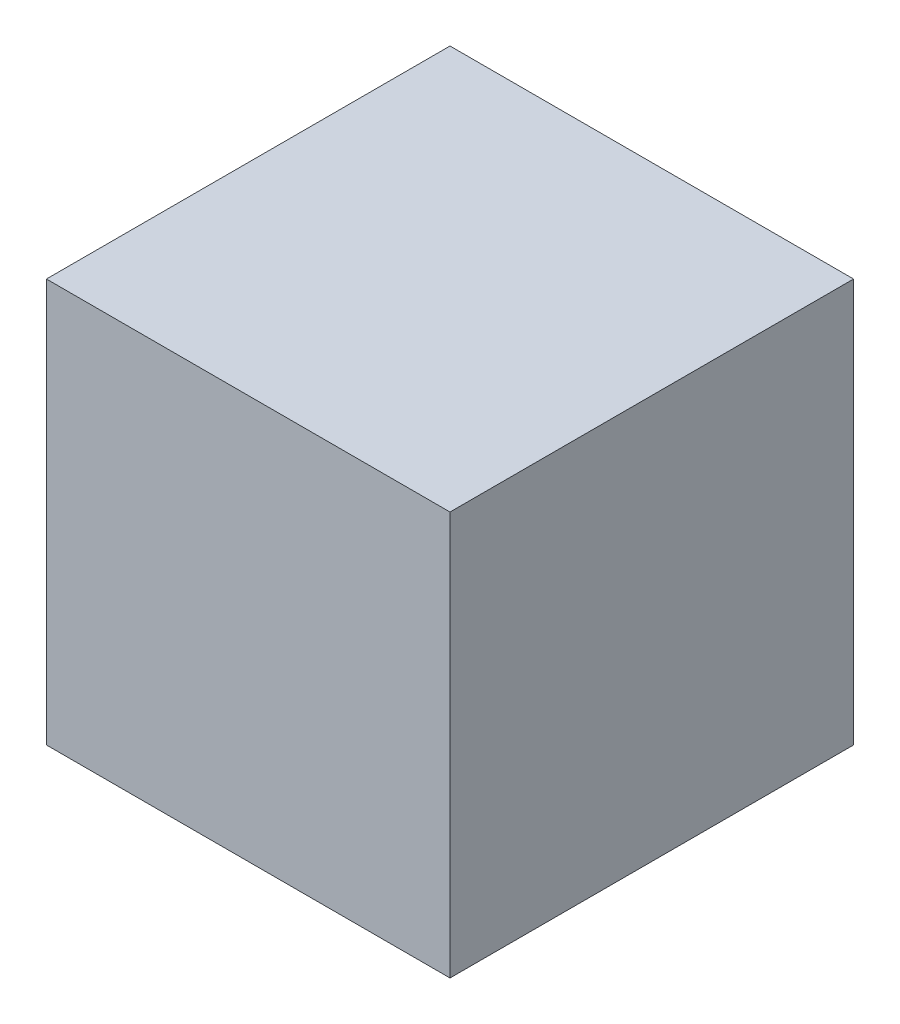
SolidWorks part; units mm, degrees
material "Plastiche personalizzate"
ref_plane "Piano frontale" through (0, 0, 0) normal (0, 0, 1) x (1, 0, 0)
ref_plane "Piano superiore" through (0, 0, 0) normal (0, 1, 0) x (1, 0, 0)
ref_plane "Piano destro" through (0, 0, 0) normal (1, 0, 0) x (0, 0, -1)
sketch "Schizzo1" plane through (0, 0, 0) normal (0, 0, 1) x (1, 0, 0)
  line L1 (50, -50) -> (-50, -50)
  line L2 (50, -50) -> (50, 50)
  line L3 (50, 50) -> (-50, 50)
  line L4 (-50, -50) -> (-50, 50)
  line L5 (50, -50) -> (-50, 50) construction
  line L6 (50, 50) -> (-50, -50) construction
  point P0 (0, 0)
  dimension "D1" = 100
  dimension "D2" = 100
extrude "Estrusione-Estrusione1" add sketch "Schizzo1" along normal blind 100
ref_plane "Piano1" through (0, 0, 0) normal (1, 0, 0) x (0, 0, -1)
ref_plane "Piano2" through (0, 0, 50) normal (0, 0, 1) x (1, 0, 0)
